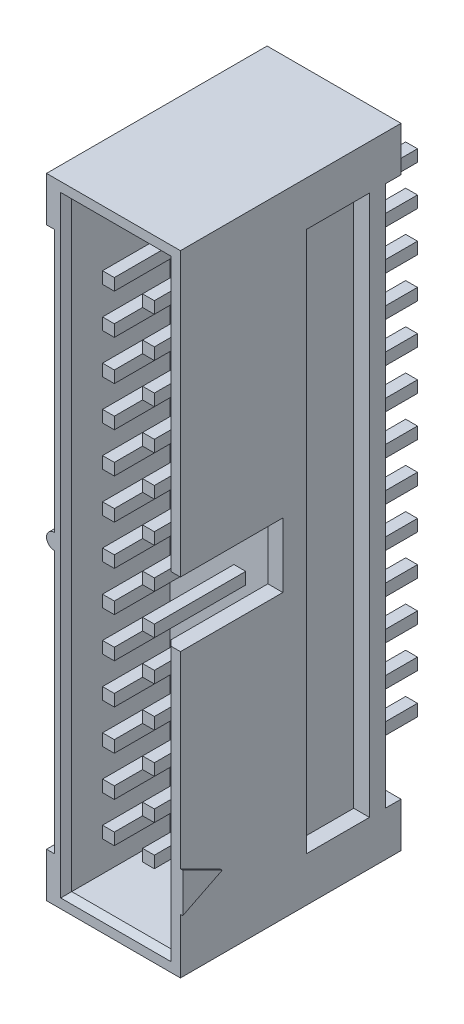
SolidWorks part; units mm, degrees
ref_plane "Front Plane" through (0, 0, 0) normal (0, 0, 1) x (1, 0, 0)
ref_plane "Top Plane" through (0, 0, 0) normal (0, 1, 0) x (1, 0, 0)
ref_plane "Right Plane" through (0, 0, 0) normal (1, 0, 0) x (0, 0, -1)
ref_plane "Plane1" through (-4.4, 0, 0) normal (-1, 0, 0) x (0, -1, 0)
sketch "Sketch1" plane through (-4.4, 0, 0) normal (-1, 0, 0) x (0, -1, 0)
  line L0 (-19.99, 1) -> (19.99, 1)
  line L1 (19.99, 1) -> (19.99, 14)
  line L2 (19.99, 14) -> (-19.99, 14)
  line L3 (-19.99, 14) -> (-19.99, 1)
extrude "Boss-Extrude1" add sketch "Sketch1" against normal blind 8.5
sketch "Sketch2" plane through (0, 0, 14) normal (0, 0, 1) x (1, 0, 0)
  line L0 (-3.9, -19.99) -> (-3.9, 17.16)
  line L1 (-3.9, 17.16) -> (-4.4, 17.16)
  line L2 (-4.4, 17.16) -> (-4.4, -19.99)
  line L3 (-4.4, -19.99) -> (-3.9, -19.99)
extrude "Cut-Extrude1" cut sketch "Sketch2" against normal through all
sketch "Sketch3" plane through (0, 0, 1) normal (0, 0, -1) x (-1, 0, 0)
  line L0 (-4.1, 19.99) -> (4.4, 19.99)
  line L1 (4.4, 19.99) -> (4.4, 17.16)
  line L2 (4.4, 17.16) -> (-4.1, 17.16)
  line L3 (-4.1, 17.16) -> (-4.1, 19.99)
extrude "Boss-Extrude2" add sketch "Sketch3" along normal blind 1
sketch "Sketch4" plane through (-3.9, 0, 0) normal (-1, 0, 0) x (0, 0, 1)
  line L0 (1, -19.99) -> (1, -17.16)
  line L1 (1, -17.16) -> (14, -17.16)
  line L2 (14, -17.16) -> (14, -19.99)
  line L3 (14, -19.99) -> (1, -19.99)
extrude "Boss-Extrude3" add sketch "Sketch4" along normal blind 0.5
sketch "Sketch5" plane through (0, 0, 1) normal (0, 0, -1) x (-1, 0, 0)
  line L0 (4.4, -19.99) -> (-4.1, -19.99)
  line L1 (-4.1, -19.99) -> (-4.1, -17.16)
  line L2 (-4.1, -17.16) -> (4.4, -17.16)
  line L3 (4.4, -17.16) -> (4.4, -19.99)
extrude "Boss-Extrude4" add sketch "Sketch5" along normal blind 1
ref_plane "Plane2" through (0, 0, 14) normal (0, 0, 1) x (1, 0, 0)
sketch "Sketch6" plane through (0, 0, 14) normal (0, 0, 1) x (1, 0, 0)
  line L0 (-3.9, -0.5) -> (-3.9, 0.5)
  arc A0 (-3.9, 0.5) -> (-3.9, -0.5) centre (-3.9, 0) ccw
extrude "Boss-Extrude5" add sketch "Sketch6" against normal blind 8.1
sketch "Sketch7" plane through (-3.9, 0, 0) normal (-1, 0, 0) x (0, 0, 1)
  line L0 (1, 17.16) -> (1, -17.16)
  line L1 (1, -17.16) -> (5.9, -17.16)
  line L2 (5.9, -17.16) -> (5.9, 17.16)
  line L3 (5.9, 17.16) -> (1, 17.16)
extrude "Cut-Extrude2" cut sketch "Sketch7" against normal blind 0.5
sketch "Sketch8" plane through (0, 0, 1) normal (0, 0, -1) x (-1, 0, 0)
  line L0 (-3.1, -17.05) -> (-3.1, 17.05)
  line L1 (-3.1, 17.05) -> (3.4, 17.05)
  line L2 (3.4, 17.05) -> (3.4, -17.05)
  line L3 (3.4, -17.05) -> (-3.1, -17.05)
extrude "Boss-Extrude6" add sketch "Sketch8" along normal blind 1
sketch "Sketch9" plane through (-3.4, 0, 0) normal (-1, 0, 0) x (0, 0, 1)
  line L0 (0.5, -17.05) -> (0.5, -17.01)
  line L1 (0.5, -17.01) -> (0, -17.01)
  line L2 (0, -17.01) -> (0, -17.05)
  line L3 (0, -17.05) -> (0.5, -17.05)
extrude "Cut-Extrude3" cut sketch "Sketch9" against normal blind 6.5
sketch "Sketch10" plane through (-3.4, 0, 0) normal (-1, 0, 0) x (0, 0, 1)
  line L0 (0, -14.47) -> (0, -16.01)
  line L1 (0, -16.01) -> (0.5, -16.01)
  line L2 (0.5, -16.01) -> (0.5, -14.47)
  line L3 (0.5, -14.47) -> (0, -14.47)
extrude "Cut-Extrude4" cut sketch "Sketch10" against normal through all
sketch "Sketch11" plane through (-3.4, 0, 0) normal (-1, 0, 0) x (0, 0, 1)
  line L0 (0, -11.93) -> (0, -13.47)
  line L1 (0, -13.47) -> (0.5, -13.47)
  line L2 (0.5, -13.47) -> (0.5, -11.93)
  line L3 (0.5, -11.93) -> (0, -11.93)
extrude "Cut-Extrude5" cut sketch "Sketch11" against normal through all
sketch "Sketch12" plane through (-3.4, 0, 0) normal (-1, 0, 0) x (0, 0, 1)
  line L0 (0, -9.39) -> (0, -10.93)
  line L1 (0, -10.93) -> (0.5, -10.93)
  line L2 (0.5, -10.93) -> (0.5, -9.39)
  line L3 (0.5, -9.39) -> (0, -9.39)
extrude "Cut-Extrude6" cut sketch "Sketch12" against normal through all
sketch "Sketch13" plane through (-3.4, 0, 0) normal (-1, 0, 0) x (0, 0, 1)
  line L0 (0, -6.85) -> (0, -8.39)
  line L1 (0, -8.39) -> (0.5, -8.39)
  line L2 (0.5, -8.39) -> (0.5, -6.85)
  line L3 (0.5, -6.85) -> (0, -6.85)
extrude "Cut-Extrude7" cut sketch "Sketch13" against normal through all
sketch "Sketch14" plane through (-3.4, 0, 0) normal (-1, 0, 0) x (0, 0, 1)
  line L0 (0, -4.31) -> (0, -5.85)
  line L1 (0, -5.85) -> (0.5, -5.85)
  line L2 (0.5, -5.85) -> (0.5, -4.31)
  line L3 (0.5, -4.31) -> (0, -4.31)
extrude "Cut-Extrude8" cut sketch "Sketch14" against normal through all
sketch "Sketch15" plane through (-3.4, 0, 0) normal (-1, 0, 0) x (0, 0, 1)
  line L0 (0, -1.77) -> (0, -3.31)
  line L1 (0, -3.31) -> (0.5, -3.31)
  line L2 (0.5, -3.31) -> (0.5, -1.77)
  line L3 (0.5, -1.77) -> (0, -1.77)
extrude "Cut-Extrude9" cut sketch "Sketch15" against normal through all
sketch "Sketch16" plane through (-3.4, 0, 0) normal (-1, 0, 0) x (0, 0, 1)
  line L0 (0, 0.77) -> (0, -0.77)
  line L1 (0, -0.77) -> (0.5, -0.77)
  line L2 (0.5, -0.77) -> (0.5, 0.77)
  line L3 (0.5, 0.77) -> (0, 0.77)
extrude "Cut-Extrude10" cut sketch "Sketch16" against normal through all
sketch "Sketch17" plane through (-3.4, 0, 0) normal (-1, 0, 0) x (0, 0, 1)
  line L0 (0, 3.31) -> (0, 1.77)
  line L1 (0, 1.77) -> (0.5, 1.77)
  line L2 (0.5, 1.77) -> (0.5, 3.31)
  line L3 (0.5, 3.31) -> (0, 3.31)
extrude "Cut-Extrude11" cut sketch "Sketch17" against normal through all
sketch "Sketch18" plane through (-3.4, 0, 0) normal (-1, 0, 0) x (0, 0, 1)
  line L0 (0, 5.85) -> (0, 4.31)
  line L1 (0, 4.31) -> (0.5, 4.31)
  line L2 (0.5, 4.31) -> (0.5, 5.85)
  line L3 (0.5, 5.85) -> (0, 5.85)
extrude "Cut-Extrude12" cut sketch "Sketch18" against normal through all
sketch "Sketch19" plane through (-3.4, 0, 0) normal (-1, 0, 0) x (0, 0, 1)
  line L0 (0, 8.39) -> (0, 6.85)
  line L1 (0, 6.85) -> (0.5, 6.85)
  line L2 (0.5, 6.85) -> (0.5, 8.39)
  line L3 (0.5, 8.39) -> (0, 8.39)
extrude "Cut-Extrude13" cut sketch "Sketch19" against normal through all
sketch "Sketch20" plane through (-3.4, 0, 0) normal (-1, 0, 0) x (0, 0, 1)
  line L0 (0, 10.93) -> (0, 9.39)
  line L1 (0, 9.39) -> (0.5, 9.39)
  line L2 (0.5, 9.39) -> (0.5, 10.93)
  line L3 (0.5, 10.93) -> (0, 10.93)
extrude "Cut-Extrude14" cut sketch "Sketch20" against normal through all
sketch "Sketch21" plane through (-3.4, 0, 0) normal (-1, 0, 0) x (0, 0, 1)
  line L0 (0, 13.47) -> (0, 11.93)
  line L1 (0, 11.93) -> (0.5, 11.93)
  line L2 (0.5, 11.93) -> (0.5, 13.47)
  line L3 (0.5, 13.47) -> (0, 13.47)
extrude "Cut-Extrude15" cut sketch "Sketch21" against normal through all
sketch "Sketch22" plane through (-3.4, 0, 0) normal (-1, 0, 0) x (0, 0, 1)
  line L0 (0, 16.01) -> (0, 14.47)
  line L1 (0, 14.47) -> (0.5, 14.47)
  line L2 (0.5, 14.47) -> (0.5, 16.01)
  line L3 (0.5, 16.01) -> (0, 16.01)
extrude "Cut-Extrude16" cut sketch "Sketch22" against normal through all
sketch "Sketch23" plane through (-3.4, 0, 0) normal (-1, 0, 0) x (0, 0, 1)
  line L0 (0, 17.05) -> (0, 17.01)
  line L1 (0, 17.01) -> (0.5, 17.01)
  line L2 (0.5, 17.01) -> (0.5, 17.05)
  line L3 (0.5, 17.05) -> (0, 17.05)
extrude "Cut-Extrude17" cut sketch "Sketch23" against normal blind 6.5
sketch "Sketch24" plane through (0, 0, 14) normal (0, 0, 1) x (1, 0, 0)
  line L0 (-3.15, -19.04) -> (3.15, -19.04)
  line L1 (3.15, -19.04) -> (3.15, 19.04)
  line L2 (3.15, 19.04) -> (-3.15, 19.04)
  line L3 (-3.15, 19.04) -> (-3.15, -19.04)
extrude "Cut-Extrude18" cut sketch "Sketch24" against normal blind 6.6
sketch "Sketch25" plane through (4.1, 0, 0) normal (1, 0, 0) x (0, 0, -1)
  line L0 (-14, -2.05) -> (-7.5, -2.05)
  line L1 (-7.5, -2.05) -> (-7.5, 2.05)
  line L2 (-7.5, 2.05) -> (-14, 2.05)
  line L3 (-14, 2.05) -> (-14, -2.05)
extrude "Cut-Extrude19" cut sketch "Sketch25" against normal up to next
sketch "Sketch26" plane through (4.1, 0, 0) normal (1, 0, 0) x (0, 0, -1)
  line L0 (-14, -13.99) -> (-11.5, -15.24)
  line L1 (-11.5, -15.24) -> (-14, -16.49)
  line L2 (-14, -16.49) -> (-14, -13.99)
extrude "Boss-Extrude7" add sketch "Sketch26" along normal blind 0.15
sketch "Sketch27" plane through (0, 0, 0.5) normal (0, 0, -1) x (-1, 0, 0)
  line L0 (-1.645, 0.375) -> (-0.895, 0.375)
  line L1 (-0.895, 0.375) -> (-0.895, -0.375)
  line L2 (-0.895, -0.375) -> (-1.645, -0.375)
  line L3 (-1.645, -0.375) -> (-1.645, 0.375)
extrude "Boss-Extrude8" add sketch "Sketch27" along normal blind 4
sketch "Sketch28" plane through (0, 0, 0.5) normal (0, 0, -1) x (-1, 0, 0)
  line L0 (0.895, 0.375) -> (1.645, 0.375)
  line L1 (1.645, 0.375) -> (1.645, -0.375)
  line L2 (1.645, -0.375) -> (0.895, -0.375)
  line L3 (0.895, -0.375) -> (0.895, 0.375)
extrude "Boss-Extrude9" add sketch "Sketch28" along normal blind 4
sketch "Sketch29" plane through (0, 0, 0.5) normal (0, 0, -1) x (-1, 0, 0)
  line L0 (-1.645, -2.165) -> (-0.895, -2.165)
  line L1 (-0.895, -2.165) -> (-0.895, -2.915)
  line L2 (-0.895, -2.915) -> (-1.645, -2.915)
  line L3 (-1.645, -2.915) -> (-1.645, -2.165)
extrude "Boss-Extrude10" add sketch "Sketch29" along normal blind 4
sketch "Sketch30" plane through (0, 0, 0.5) normal (0, 0, -1) x (-1, 0, 0)
  line L0 (0.895, -2.165) -> (1.645, -2.165)
  line L1 (1.645, -2.165) -> (1.645, -2.915)
  line L2 (1.645, -2.915) -> (0.895, -2.915)
  line L3 (0.895, -2.915) -> (0.895, -2.165)
extrude "Boss-Extrude11" add sketch "Sketch30" along normal blind 4
sketch "Sketch31" plane through (0, 0, 0.5) normal (0, 0, -1) x (-1, 0, 0)
  line L0 (-1.645, 2.915) -> (-0.895, 2.915)
  line L1 (-0.895, 2.915) -> (-0.895, 2.165)
  line L2 (-0.895, 2.165) -> (-1.645, 2.165)
  line L3 (-1.645, 2.165) -> (-1.645, 2.915)
extrude "Boss-Extrude12" add sketch "Sketch31" along normal blind 4
sketch "Sketch32" plane through (0, 0, 0.5) normal (0, 0, -1) x (-1, 0, 0)
  line L0 (0.895, 2.915) -> (1.645, 2.915)
  line L1 (1.645, 2.915) -> (1.645, 2.165)
  line L2 (1.645, 2.165) -> (0.895, 2.165)
  line L3 (0.895, 2.165) -> (0.895, 2.915)
extrude "Boss-Extrude13" add sketch "Sketch32" along normal blind 4
sketch "Sketch33" plane through (0, 0, 0.5) normal (0, 0, -1) x (-1, 0, 0)
  line L0 (-1.645, -4.705) -> (-0.895, -4.705)
  line L1 (-0.895, -4.705) -> (-0.895, -5.455)
  line L2 (-0.895, -5.455) -> (-1.645, -5.455)
  line L3 (-1.645, -5.455) -> (-1.645, -4.705)
extrude "Boss-Extrude14" add sketch "Sketch33" along normal blind 4
sketch "Sketch34" plane through (0, 0, 0.5) normal (0, 0, -1) x (-1, 0, 0)
  line L0 (0.895, -4.705) -> (1.645, -4.705)
  line L1 (1.645, -4.705) -> (1.645, -5.455)
  line L2 (1.645, -5.455) -> (0.895, -5.455)
  line L3 (0.895, -5.455) -> (0.895, -4.705)
extrude "Boss-Extrude15" add sketch "Sketch34" along normal blind 4
sketch "Sketch35" plane through (0, 0, 0.5) normal (0, 0, -1) x (-1, 0, 0)
  line L0 (-1.645, 5.455) -> (-0.895, 5.455)
  line L1 (-0.895, 5.455) -> (-0.895, 4.705)
  line L2 (-0.895, 4.705) -> (-1.645, 4.705)
  line L3 (-1.645, 4.705) -> (-1.645, 5.455)
extrude "Boss-Extrude16" add sketch "Sketch35" along normal blind 4
sketch "Sketch36" plane through (0, 0, 0.5) normal (0, 0, -1) x (-1, 0, 0)
  line L0 (0.895, 5.455) -> (1.645, 5.455)
  line L1 (1.645, 5.455) -> (1.645, 4.705)
  line L2 (1.645, 4.705) -> (0.895, 4.705)
  line L3 (0.895, 4.705) -> (0.895, 5.455)
extrude "Boss-Extrude17" add sketch "Sketch36" along normal blind 4
sketch "Sketch37" plane through (0, 0, 0.5) normal (0, 0, -1) x (-1, 0, 0)
  line L0 (-1.645, -7.245) -> (-0.895, -7.245)
  line L1 (-0.895, -7.245) -> (-0.895, -7.995)
  line L2 (-0.895, -7.995) -> (-1.645, -7.995)
  line L3 (-1.645, -7.995) -> (-1.645, -7.245)
extrude "Boss-Extrude18" add sketch "Sketch37" along normal blind 4
sketch "Sketch38" plane through (0, 0, 0.5) normal (0, 0, -1) x (-1, 0, 0)
  line L0 (0.895, -7.245) -> (1.645, -7.245)
  line L1 (1.645, -7.245) -> (1.645, -7.995)
  line L2 (1.645, -7.995) -> (0.895, -7.995)
  line L3 (0.895, -7.995) -> (0.895, -7.245)
extrude "Boss-Extrude19" add sketch "Sketch38" along normal blind 4
sketch "Sketch39" plane through (0, 0, 0.5) normal (0, 0, -1) x (-1, 0, 0)
  line L0 (-1.645, 7.995) -> (-0.895, 7.995)
  line L1 (-0.895, 7.995) -> (-0.895, 7.245)
  line L2 (-0.895, 7.245) -> (-1.645, 7.245)
  line L3 (-1.645, 7.245) -> (-1.645, 7.995)
extrude "Boss-Extrude20" add sketch "Sketch39" along normal blind 4
sketch "Sketch40" plane through (0, 0, 0.5) normal (0, 0, -1) x (-1, 0, 0)
  line L0 (0.895, 7.995) -> (1.645, 7.995)
  line L1 (1.645, 7.995) -> (1.645, 7.245)
  line L2 (1.645, 7.245) -> (0.895, 7.245)
  line L3 (0.895, 7.245) -> (0.895, 7.995)
extrude "Boss-Extrude21" add sketch "Sketch40" along normal blind 4
sketch "Sketch41" plane through (0, 0, 0.5) normal (0, 0, -1) x (-1, 0, 0)
  line L0 (-1.645, -9.785) -> (-0.895, -9.785)
  line L1 (-0.895, -9.785) -> (-0.895, -10.535)
  line L2 (-0.895, -10.535) -> (-1.645, -10.535)
  line L3 (-1.645, -10.535) -> (-1.645, -9.785)
extrude "Boss-Extrude22" add sketch "Sketch41" along normal blind 4
sketch "Sketch42" plane through (0, 0, 0.5) normal (0, 0, -1) x (-1, 0, 0)
  line L0 (0.895, -9.785) -> (1.645, -9.785)
  line L1 (1.645, -9.785) -> (1.645, -10.535)
  line L2 (1.645, -10.535) -> (0.895, -10.535)
  line L3 (0.895, -10.535) -> (0.895, -9.785)
extrude "Boss-Extrude23" add sketch "Sketch42" along normal blind 4
sketch "Sketch43" plane through (0, 0, 0.5) normal (0, 0, -1) x (-1, 0, 0)
  line L0 (-1.645, 10.535) -> (-0.895, 10.535)
  line L1 (-0.895, 10.535) -> (-0.895, 9.785)
  line L2 (-0.895, 9.785) -> (-1.645, 9.785)
  line L3 (-1.645, 9.785) -> (-1.645, 10.535)
extrude "Boss-Extrude24" add sketch "Sketch43" along normal blind 4
sketch "Sketch44" plane through (0, 0, 0.5) normal (0, 0, -1) x (-1, 0, 0)
  line L0 (0.895, 10.535) -> (1.645, 10.535)
  line L1 (1.645, 10.535) -> (1.645, 9.785)
  line L2 (1.645, 9.785) -> (0.895, 9.785)
  line L3 (0.895, 9.785) -> (0.895, 10.535)
extrude "Boss-Extrude25" add sketch "Sketch44" along normal blind 4
sketch "Sketch45" plane through (0, 0, 0.5) normal (0, 0, -1) x (-1, 0, 0)
  line L0 (-1.645, -12.325) -> (-0.895, -12.325)
  line L1 (-0.895, -12.325) -> (-0.895, -13.075)
  line L2 (-0.895, -13.075) -> (-1.645, -13.075)
  line L3 (-1.645, -13.075) -> (-1.645, -12.325)
extrude "Boss-Extrude26" add sketch "Sketch45" along normal blind 4
sketch "Sketch46" plane through (0, 0, 0.5) normal (0, 0, -1) x (-1, 0, 0)
  line L0 (0.895, -12.325) -> (1.645, -12.325)
  line L1 (1.645, -12.325) -> (1.645, -13.075)
  line L2 (1.645, -13.075) -> (0.895, -13.075)
  line L3 (0.895, -13.075) -> (0.895, -12.325)
extrude "Boss-Extrude27" add sketch "Sketch46" along normal blind 4
sketch "Sketch47" plane through (0, 0, 0.5) normal (0, 0, -1) x (-1, 0, 0)
  line L0 (-1.645, 13.075) -> (-0.895, 13.075)
  line L1 (-0.895, 13.075) -> (-0.895, 12.325)
  line L2 (-0.895, 12.325) -> (-1.645, 12.325)
  line L3 (-1.645, 12.325) -> (-1.645, 13.075)
extrude "Boss-Extrude28" add sketch "Sketch47" along normal blind 4
sketch "Sketch48" plane through (0, 0, 0.5) normal (0, 0, -1) x (-1, 0, 0)
  line L0 (0.895, 13.075) -> (1.645, 13.075)
  line L1 (1.645, 13.075) -> (1.645, 12.325)
  line L2 (1.645, 12.325) -> (0.895, 12.325)
  line L3 (0.895, 12.325) -> (0.895, 13.075)
extrude "Boss-Extrude29" add sketch "Sketch48" along normal blind 4
sketch "Sketch49" plane through (0, 0, 0.5) normal (0, 0, -1) x (-1, 0, 0)
  line L0 (-1.645, -14.865) -> (-0.895, -14.865)
  line L1 (-0.895, -14.865) -> (-0.895, -15.615)
  line L2 (-0.895, -15.615) -> (-1.645, -15.615)
  line L3 (-1.645, -15.615) -> (-1.645, -14.865)
extrude "Boss-Extrude30" add sketch "Sketch49" along normal blind 4
sketch "Sketch50" plane through (0, 0, 0.5) normal (0, 0, -1) x (-1, 0, 0)
  line L0 (0.895, -14.865) -> (1.645, -14.865)
  line L1 (1.645, -14.865) -> (1.645, -15.615)
  line L2 (1.645, -15.615) -> (0.895, -15.615)
  line L3 (0.895, -15.615) -> (0.895, -14.865)
extrude "Boss-Extrude31" add sketch "Sketch50" along normal blind 4
sketch "Sketch51" plane through (0, 0, 0.5) normal (0, 0, -1) x (-1, 0, 0)
  line L0 (-1.645, 15.615) -> (-0.895, 15.615)
  line L1 (-0.895, 15.615) -> (-0.895, 14.865)
  line L2 (-0.895, 14.865) -> (-1.645, 14.865)
  line L3 (-1.645, 14.865) -> (-1.645, 15.615)
extrude "Boss-Extrude32" add sketch "Sketch51" along normal blind 4
sketch "Sketch52" plane through (0, 0, 0.5) normal (0, 0, -1) x (-1, 0, 0)
  line L0 (0.895, 15.615) -> (1.645, 15.615)
  line L1 (1.645, 15.615) -> (1.645, 14.865)
  line L2 (1.645, 14.865) -> (0.895, 14.865)
  line L3 (0.895, 14.865) -> (0.895, 15.615)
extrude "Boss-Extrude33" add sketch "Sketch52" along normal blind 4
sketch "Sketch53" plane through (0, 0, 7.4) normal (0, 0, 1) x (1, 0, 0)
  line L0 (1.645, -15.615) -> (0.895, -15.615)
  line L1 (0.895, -15.615) -> (0.895, -14.865)
  line L2 (0.895, -14.865) -> (1.645, -14.865)
  line L3 (1.645, -14.865) -> (1.645, -15.615)
extrude "Boss-Extrude34" add sketch "Sketch53" along normal blind 5.8
sketch "Sketch54" plane through (0, 0, 7.4) normal (0, 0, 1) x (1, 0, 0)
  line L0 (-0.895, -15.615) -> (-1.645, -15.615)
  line L1 (-1.645, -15.615) -> (-1.645, -14.865)
  line L2 (-1.645, -14.865) -> (-0.895, -14.865)
  line L3 (-0.895, -14.865) -> (-0.895, -15.615)
extrude "Boss-Extrude35" add sketch "Sketch54" along normal blind 5.8
sketch "Sketch55" plane through (0, 0, 7.4) normal (0, 0, 1) x (1, 0, 0)
  line L0 (1.645, -13.075) -> (0.895, -13.075)
  line L1 (0.895, -13.075) -> (0.895, -12.325)
  line L2 (0.895, -12.325) -> (1.645, -12.325)
  line L3 (1.645, -12.325) -> (1.645, -13.075)
extrude "Boss-Extrude36" add sketch "Sketch55" along normal blind 5.8
sketch "Sketch56" plane through (0, 0, 7.4) normal (0, 0, 1) x (1, 0, 0)
  line L0 (-0.895, -13.075) -> (-1.645, -13.075)
  line L1 (-1.645, -13.075) -> (-1.645, -12.325)
  line L2 (-1.645, -12.325) -> (-0.895, -12.325)
  line L3 (-0.895, -12.325) -> (-0.895, -13.075)
extrude "Boss-Extrude37" add sketch "Sketch56" along normal blind 5.8
sketch "Sketch57" plane through (0, 0, 7.4) normal (0, 0, 1) x (1, 0, 0)
  line L0 (1.645, -10.535) -> (0.895, -10.535)
  line L1 (0.895, -10.535) -> (0.895, -9.785)
  line L2 (0.895, -9.785) -> (1.645, -9.785)
  line L3 (1.645, -9.785) -> (1.645, -10.535)
extrude "Boss-Extrude38" add sketch "Sketch57" along normal blind 5.8
sketch "Sketch58" plane through (0, 0, 7.4) normal (0, 0, 1) x (1, 0, 0)
  line L0 (-0.895, -10.535) -> (-1.645, -10.535)
  line L1 (-1.645, -10.535) -> (-1.645, -9.785)
  line L2 (-1.645, -9.785) -> (-0.895, -9.785)
  line L3 (-0.895, -9.785) -> (-0.895, -10.535)
extrude "Boss-Extrude39" add sketch "Sketch58" along normal blind 5.8
sketch "Sketch59" plane through (0, 0, 7.4) normal (0, 0, 1) x (1, 0, 0)
  line L0 (1.645, -7.995) -> (0.895, -7.995)
  line L1 (0.895, -7.995) -> (0.895, -7.245)
  line L2 (0.895, -7.245) -> (1.645, -7.245)
  line L3 (1.645, -7.245) -> (1.645, -7.995)
extrude "Boss-Extrude40" add sketch "Sketch59" along normal blind 5.8
sketch "Sketch60" plane through (0, 0, 7.4) normal (0, 0, 1) x (1, 0, 0)
  line L0 (-0.895, -7.995) -> (-1.645, -7.995)
  line L1 (-1.645, -7.995) -> (-1.645, -7.245)
  line L2 (-1.645, -7.245) -> (-0.895, -7.245)
  line L3 (-0.895, -7.245) -> (-0.895, -7.995)
extrude "Boss-Extrude41" add sketch "Sketch60" along normal blind 5.8
sketch "Sketch61" plane through (0, 0, 7.4) normal (0, 0, 1) x (1, 0, 0)
  line L0 (1.645, -5.455) -> (0.895, -5.455)
  line L1 (0.895, -5.455) -> (0.895, -4.705)
  line L2 (0.895, -4.705) -> (1.645, -4.705)
  line L3 (1.645, -4.705) -> (1.645, -5.455)
extrude "Boss-Extrude42" add sketch "Sketch61" along normal blind 5.8
sketch "Sketch62" plane through (0, 0, 7.4) normal (0, 0, 1) x (1, 0, 0)
  line L0 (-0.895, -5.455) -> (-1.645, -5.455)
  line L1 (-1.645, -5.455) -> (-1.645, -4.705)
  line L2 (-1.645, -4.705) -> (-0.895, -4.705)
  line L3 (-0.895, -4.705) -> (-0.895, -5.455)
extrude "Boss-Extrude43" add sketch "Sketch62" along normal blind 5.8
sketch "Sketch63" plane through (0, 0, 7.4) normal (0, 0, 1) x (1, 0, 0)
  line L0 (1.645, -2.915) -> (0.895, -2.915)
  line L1 (0.895, -2.915) -> (0.895, -2.165)
  line L2 (0.895, -2.165) -> (1.645, -2.165)
  line L3 (1.645, -2.165) -> (1.645, -2.915)
extrude "Boss-Extrude44" add sketch "Sketch63" along normal blind 5.8
sketch "Sketch64" plane through (0, 0, 7.4) normal (0, 0, 1) x (1, 0, 0)
  line L0 (-0.895, -2.915) -> (-1.645, -2.915)
  line L1 (-1.645, -2.915) -> (-1.645, -2.165)
  line L2 (-1.645, -2.165) -> (-0.895, -2.165)
  line L3 (-0.895, -2.165) -> (-0.895, -2.915)
extrude "Boss-Extrude45" add sketch "Sketch64" along normal blind 5.8
sketch "Sketch65" plane through (0, 0, 7.4) normal (0, 0, 1) x (1, 0, 0)
  line L0 (1.645, -0.375) -> (0.895, -0.375)
  line L1 (0.895, -0.375) -> (0.895, 0.375)
  line L2 (0.895, 0.375) -> (1.645, 0.375)
  line L3 (1.645, 0.375) -> (1.645, -0.375)
extrude "Boss-Extrude46" add sketch "Sketch65" along normal blind 5.8
sketch "Sketch66" plane through (0, 0, 7.4) normal (0, 0, 1) x (1, 0, 0)
  line L0 (-0.895, -0.375) -> (-1.645, -0.375)
  line L1 (-1.645, -0.375) -> (-1.645, 0.375)
  line L2 (-1.645, 0.375) -> (-0.895, 0.375)
  line L3 (-0.895, 0.375) -> (-0.895, -0.375)
extrude "Boss-Extrude47" add sketch "Sketch66" along normal blind 5.8
sketch "Sketch67" plane through (0, 0, 7.4) normal (0, 0, 1) x (1, 0, 0)
  line L0 (1.645, 2.165) -> (0.895, 2.165)
  line L1 (0.895, 2.165) -> (0.895, 2.915)
  line L2 (0.895, 2.915) -> (1.645, 2.915)
  line L3 (1.645, 2.915) -> (1.645, 2.165)
extrude "Boss-Extrude48" add sketch "Sketch67" along normal blind 5.8
sketch "Sketch68" plane through (0, 0, 7.4) normal (0, 0, 1) x (1, 0, 0)
  line L0 (-0.895, 2.165) -> (-1.645, 2.165)
  line L1 (-1.645, 2.165) -> (-1.645, 2.915)
  line L2 (-1.645, 2.915) -> (-0.895, 2.915)
  line L3 (-0.895, 2.915) -> (-0.895, 2.165)
extrude "Boss-Extrude49" add sketch "Sketch68" along normal blind 5.8
sketch "Sketch69" plane through (0, 0, 7.4) normal (0, 0, 1) x (1, 0, 0)
  line L0 (1.645, 4.705) -> (0.895, 4.705)
  line L1 (0.895, 4.705) -> (0.895, 5.455)
  line L2 (0.895, 5.455) -> (1.645, 5.455)
  line L3 (1.645, 5.455) -> (1.645, 4.705)
extrude "Boss-Extrude50" add sketch "Sketch69" along normal blind 5.8
sketch "Sketch70" plane through (0, 0, 7.4) normal (0, 0, 1) x (1, 0, 0)
  line L0 (-0.895, 4.705) -> (-1.645, 4.705)
  line L1 (-1.645, 4.705) -> (-1.645, 5.455)
  line L2 (-1.645, 5.455) -> (-0.895, 5.455)
  line L3 (-0.895, 5.455) -> (-0.895, 4.705)
extrude "Boss-Extrude51" add sketch "Sketch70" along normal blind 5.8
sketch "Sketch71" plane through (0, 0, 7.4) normal (0, 0, 1) x (1, 0, 0)
  line L0 (1.645, 7.245) -> (0.895, 7.245)
  line L1 (0.895, 7.245) -> (0.895, 7.995)
  line L2 (0.895, 7.995) -> (1.645, 7.995)
  line L3 (1.645, 7.995) -> (1.645, 7.245)
extrude "Boss-Extrude52" add sketch "Sketch71" along normal blind 5.8
sketch "Sketch72" plane through (0, 0, 7.4) normal (0, 0, 1) x (1, 0, 0)
  line L0 (-0.895, 7.245) -> (-1.645, 7.245)
  line L1 (-1.645, 7.245) -> (-1.645, 7.995)
  line L2 (-1.645, 7.995) -> (-0.895, 7.995)
  line L3 (-0.895, 7.995) -> (-0.895, 7.245)
extrude "Boss-Extrude53" add sketch "Sketch72" along normal blind 5.8
sketch "Sketch73" plane through (0, 0, 7.4) normal (0, 0, 1) x (1, 0, 0)
  line L0 (1.645, 9.785) -> (0.895, 9.785)
  line L1 (0.895, 9.785) -> (0.895, 10.535)
  line L2 (0.895, 10.535) -> (1.645, 10.535)
  line L3 (1.645, 10.535) -> (1.645, 9.785)
extrude "Boss-Extrude54" add sketch "Sketch73" along normal blind 5.8
sketch "Sketch74" plane through (0, 0, 7.4) normal (0, 0, 1) x (1, 0, 0)
  line L0 (-0.895, 9.785) -> (-1.645, 9.785)
  line L1 (-1.645, 9.785) -> (-1.645, 10.535)
  line L2 (-1.645, 10.535) -> (-0.895, 10.535)
  line L3 (-0.895, 10.535) -> (-0.895, 9.785)
extrude "Boss-Extrude55" add sketch "Sketch74" along normal blind 5.8
sketch "Sketch75" plane through (0, 0, 7.4) normal (0, 0, 1) x (1, 0, 0)
  line L0 (1.645, 12.325) -> (0.895, 12.325)
  line L1 (0.895, 12.325) -> (0.895, 13.075)
  line L2 (0.895, 13.075) -> (1.645, 13.075)
  line L3 (1.645, 13.075) -> (1.645, 12.325)
extrude "Boss-Extrude56" add sketch "Sketch75" along normal blind 5.8
sketch "Sketch76" plane through (0, 0, 7.4) normal (0, 0, 1) x (1, 0, 0)
  line L0 (-0.895, 12.325) -> (-1.645, 12.325)
  line L1 (-1.645, 12.325) -> (-1.645, 13.075)
  line L2 (-1.645, 13.075) -> (-0.895, 13.075)
  line L3 (-0.895, 13.075) -> (-0.895, 12.325)
extrude "Boss-Extrude57" add sketch "Sketch76" along normal blind 5.8
sketch "Sketch77" plane through (0, 0, 7.4) normal (0, 0, 1) x (1, 0, 0)
  line L0 (1.645, 14.865) -> (0.895, 14.865)
  line L1 (0.895, 14.865) -> (0.895, 15.615)
  line L2 (0.895, 15.615) -> (1.645, 15.615)
  line L3 (1.645, 15.615) -> (1.645, 14.865)
extrude "Boss-Extrude58" add sketch "Sketch77" along normal blind 5.8
sketch "Sketch78" plane through (0, 0, 7.4) normal (0, 0, 1) x (1, 0, 0)
  line L0 (-0.895, 14.865) -> (-1.645, 14.865)
  line L1 (-1.645, 14.865) -> (-1.645, 15.615)
  line L2 (-1.645, 15.615) -> (-0.895, 15.615)
  line L3 (-0.895, 15.615) -> (-0.895, 14.865)
extrude "Boss-Extrude59" add sketch "Sketch78" along normal blind 5.8
sketch "Sketch79" plane through (4.1, 0, 0) normal (1, 0, 0) x (0, 0, -1)
  line L0 (-2, -17.16) -> (-2, 17.16)
  line L1 (-2, 17.16) -> (-6, 17.16)
  line L2 (-6, 17.16) -> (-6, -17.16)
  line L3 (-6, -17.16) -> (-2, -17.16)
extrude "Cut-Extrude20" cut sketch "Sketch79" against normal blind 1
chamfer "Chamfer1" distance 0.35 angle 45 5 edges at (3.15, -10.545, 14) (0, -19.04, 14) (-3.15, 0, 14) (3.15, 10.545, 14) (0, 19.04, 14)
